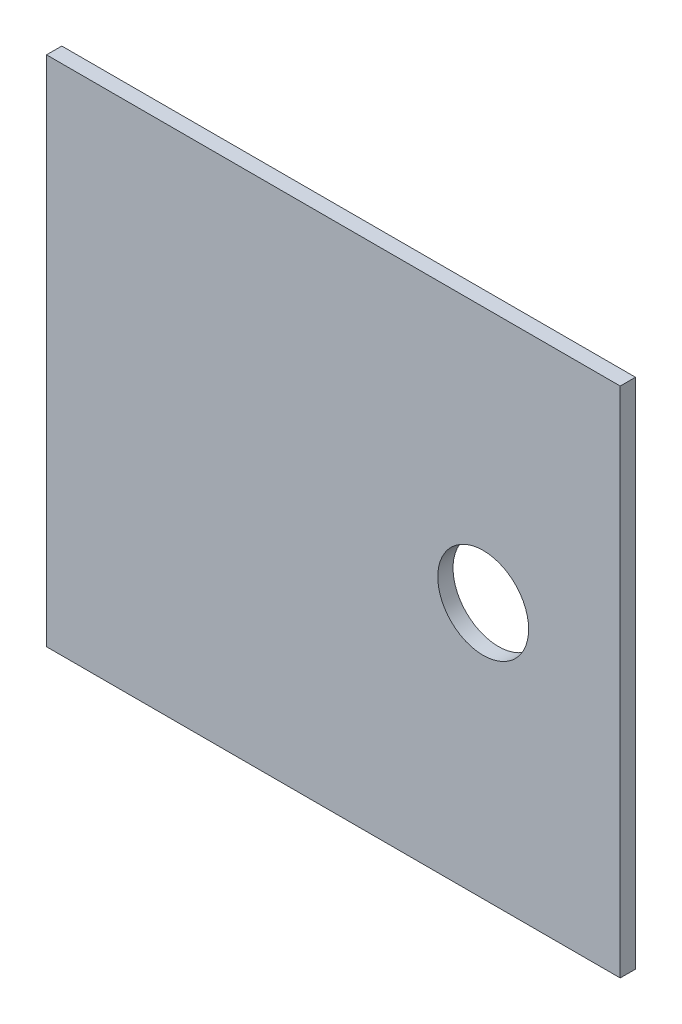
SolidWorks part; units mm, degrees
ref_plane "Alzado" through (0, 0, 0) normal (0, 0, 1) x (1, 0, 0)
ref_plane "Planta" through (0, 0, 0) normal (0, 1, 0) x (1, 0, 0)
ref_plane "Vista lateral" through (0, 0, 0) normal (1, 0, 0) x (0, 0, -1)
sketch "Croquis1" plane through (0, 0, 0) normal (0, 0, 1) x (1, 0, 0)
  line L0 (6.65, 45.25) -> (6.65, 12.25) construction
  line L1 (-64.9, 70.75) -> (29.1, 70.75)
  line L2 (-64.9, 70.75) -> (-64.9, -13.25)
  line L3 (-64.9, -13.25) -> (29.1, -13.25)
  line L4 (29.1, 70.75) -> (29.1, -13.25)
  line L6 (9.3, 12.25) -> (4, 12.25) construction
  circle A0 centre (6.65, 28.75) radius 7.4456
  point P11 (4.75, -13.25)
  point P12 (6.65, 12.25)
  point P13 (0, 0)
  point P14 (6.65, 45.25)
  point P16 (6.65, 12.25)
extrude "Saliente-Extruir1" add sketch "Croquis1" along normal blind 2.5
